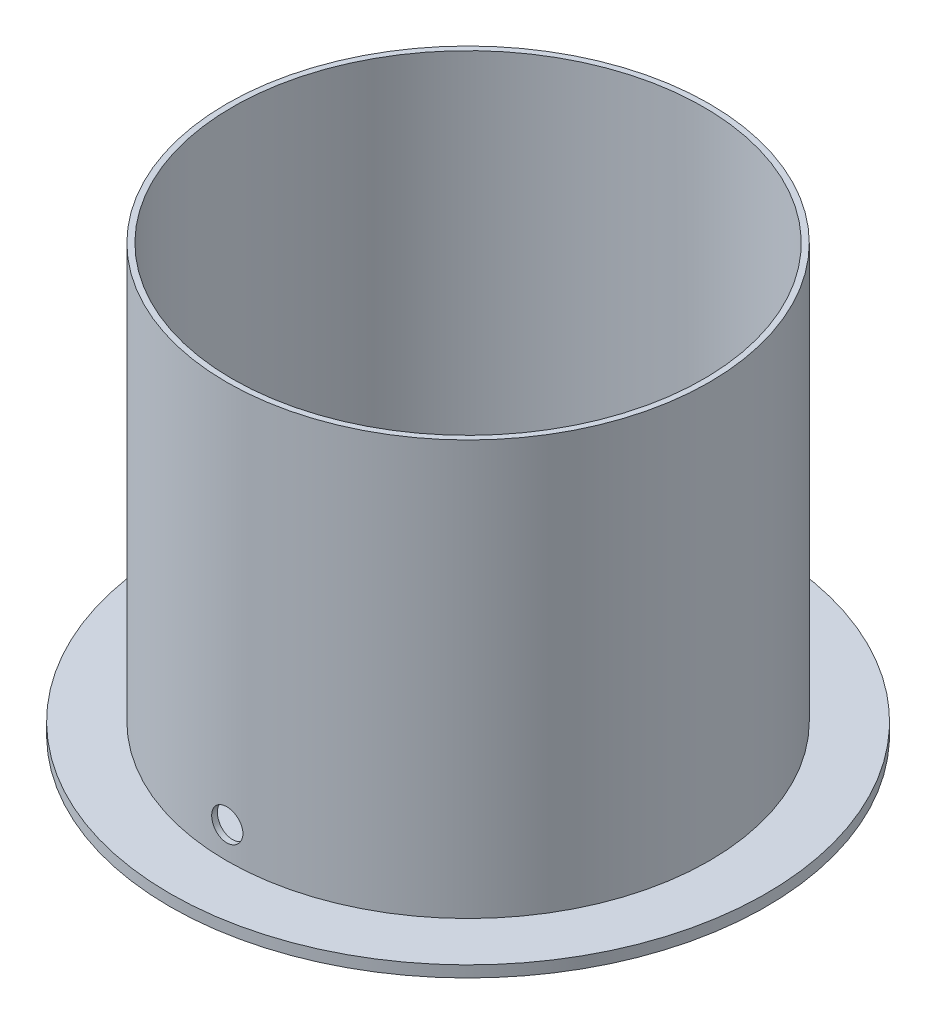
SolidWorks part; units mm, degrees
ref_plane "Front Plane" through (0, 0, 0) normal (0, 0, 1) x (1, 0, 0)
ref_plane "Top Plane" through (0, 0, 0) normal (0, 1, 0) x (1, 0, 0)
ref_plane "Right Plane" through (0, 0, 0) normal (1, 0, 0) x (0, 0, -1)
sketch "Base Flange Sketch" plane through (0, 0, 0) normal (0, 1, 0) x (1, 0, 0)
  circle A0 centre (0, 0) radius 210
  dimension "D1" = 420
extrude "Base Flange" add sketch "Base Flange Sketch" along normal blind 8
sketch "Tank Wall Sketch" plane through (0, 0, 0) normal (0, 1, 0) x (1, 0, 0)
  circle A0 centre (0, 0) radius 170
  circle A1 centre (0, 0) radius 166
  dimension "D1" = 340
  dimension "D2" = 332
extrude "Tank Wall" add sketch "Tank Wall Sketch" along normal blind 300
sketch "Port Holes Sketch" plane through (0, 0, 0) normal (0, 0, 1) x (1, 0, 0)
  circle A0 centre (0, 30) radius 11
  dimension "D2" = 22
  dimension "D1" = 30
extrude "Tap + Drain Ports" cut sketch "Port Holes Sketch" against normal through all both and the other way through all
